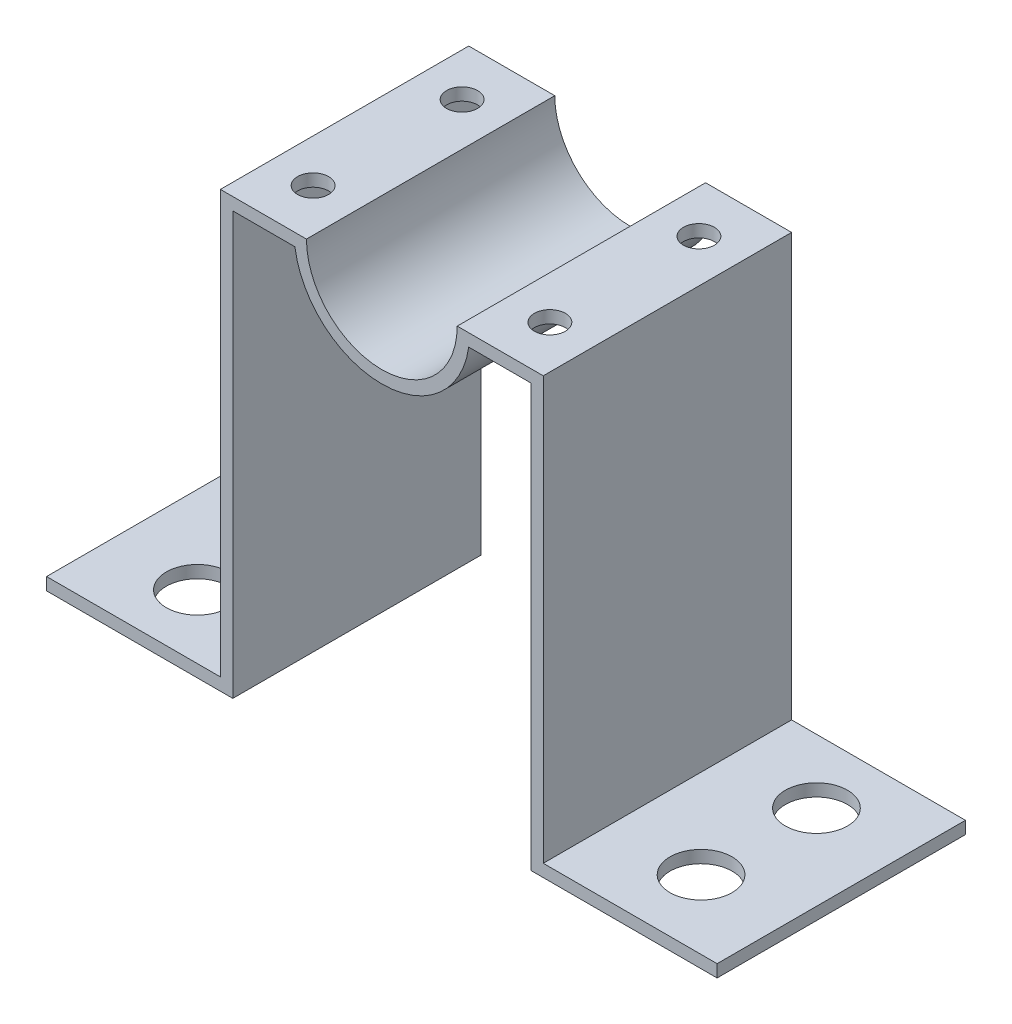
SolidWorks part; units mm, degrees
material "Plain Carbon Steel"
ref_plane "Front Plane" through (0, 0, 0) normal (0, 0, 1) x (1, 0, 0)
ref_plane "Top Plane" through (0, 0, 0) normal (0, 1, 0) x (1, 0, 0)
ref_plane "Right Plane" through (0, 0, 0) normal (1, 0, 0) x (0, 0, -1)
sketch "Sketch2" plane through (0, 0, 0) normal (0, 1, 0) x (1, 0, 0)
  line L1 (0, 0) -> (38.1, 0)
  line L2 (0, 0) -> (0, 50.8)
  line L3 (0, 50.8) -> (38.1, 50.8)
  line L4 (38.1, 0) -> (38.1, 50.8)
  dimension "D1" = 38.1
  dimension "D2" = 50.8
extrude "Boss-Extrude1" add sketch "Sketch2" along normal blind 2.54
sketch "Sketch6" plane through (0, 2.54, 0) normal (0, 1, 0) x (-1, 0, 0)
  line L0 (-38.1, -50.8) -> (0, -50.8) construction
  line L1 (-38.1, 0) -> (-35.56, 0)
  line L2 (-38.1, 0) -> (-38.1, -50.8)
  line L3 (-38.1, -50.8) -> (-35.56, -50.8)
  line L4 (-35.56, 0) -> (-35.56, -50.8)
  dimension "D1" = 2.54
extrude "Boss-Extrude2" add sketch "Sketch6" along normal blind 86.36
sketch "Sketch7" plane through (0, 0, 0) normal (0, 0, 1) x (1, 0, 0)
  line L0 (68.58, 73.4795) -> (68.58, 70.9395)
  line L1 (38.1, 88.9) -> (53.1595, 88.9)
  line L2 (50.8, 86.36) -> (38.1, 86.36)
  line L3 (38.1, 88.9) -> (38.1, 86.36)
  arc A0 (53.1595, 88.9) -> (68.58, 73.4795) centre (68.58, 88.9) ccw
  arc A1 (68.58, 70.9395) -> (50.8, 86.36) centre (68.58, 88.9) cw
  dimension "D1" = 30.48
  dimension "D2" = 12.7
  dimension "D3" = 2.54
extrude "Boss-Extrude3" add sketch "Sketch7" against normal up to vertex (50.8 mm away) up to point (38.1, 88.9, -50.8)
mirror "Mirror4" about plane through (68.58, 73.4795, -50.8) normal (1, 0, 0) of bodies 104
sketch "Sketch8" plane through (0, 2.54, 0) normal (0, 1, 0) x (-1, 0, 0)
  line L0 (-17.78, -13.081) -> (0, -13.081) construction
  line L1 (0, -50.8) -> (0, 0) construction
  line L2 (-17.78, -13.081) -> (-35.56, -13.081) construction
  line L3 (-35.56, -50.8) -> (-35.56, 0) construction
  line L4 (-17.78, -13.081) -> (-17.78, 0) construction
  line L5 (0, 0) -> (-35.56, 0) construction
  line L6 (-17.78, -37.719) -> (-17.78, -50.8) construction
  line L7 (-35.56, -50.8) -> (0, -50.8) construction
  circle A0 centre (-17.78, -13.081) radius 6.35
  circle A1 centre (-17.78, -37.719) radius 6.35
  circle A2 centre (-119.7641, -37.719) radius 6.35
  circle A3 centre (-119.7641, -14.1142) radius 6.35
  dimension "D1" = 12.7
extrude "Cut-Extrude1" cut sketch "Sketch8" against normal up to next
sketch "Sketch9" plane through (0, 88.9, 0) normal (0, 1, 0) x (-1, 0, 0)
  line L0 (-44.3597, -10.16) -> (-44.3597, 0) construction
  line L3 (-92.8003, -10.16) -> (-92.8003, 0) construction
  line L4 (-101.6, 0) -> (-84.0005, 0) construction
  line L5 (-92.8003, -50.8) -> (-92.8003, -40.64) construction
  line L6 (-84.0005, -50.8) -> (-101.6, -50.8) construction
  line L7 (-44.3597, -50.8) -> (-44.3597, -40.64) construction
  line L8 (-35.56, 0) -> (-53.1595, 0) construction
  line L9 (-53.1595, -50.8) -> (-35.56, -50.8) construction
  circle A0 centre (-92.8003, -10.16) radius 3.175
  circle A1 centre (-92.8003, -40.64) radius 3.175
  circle A2 centre (-44.3597, -10.16) radius 3.175
  circle A3 centre (-44.3597, -40.64) radius 3.175
  dimension "D2" = 6.35
  dimension "D1" = 10.16
extrude "Cut-Extrude2" cut sketch "Sketch9" against normal up to next
